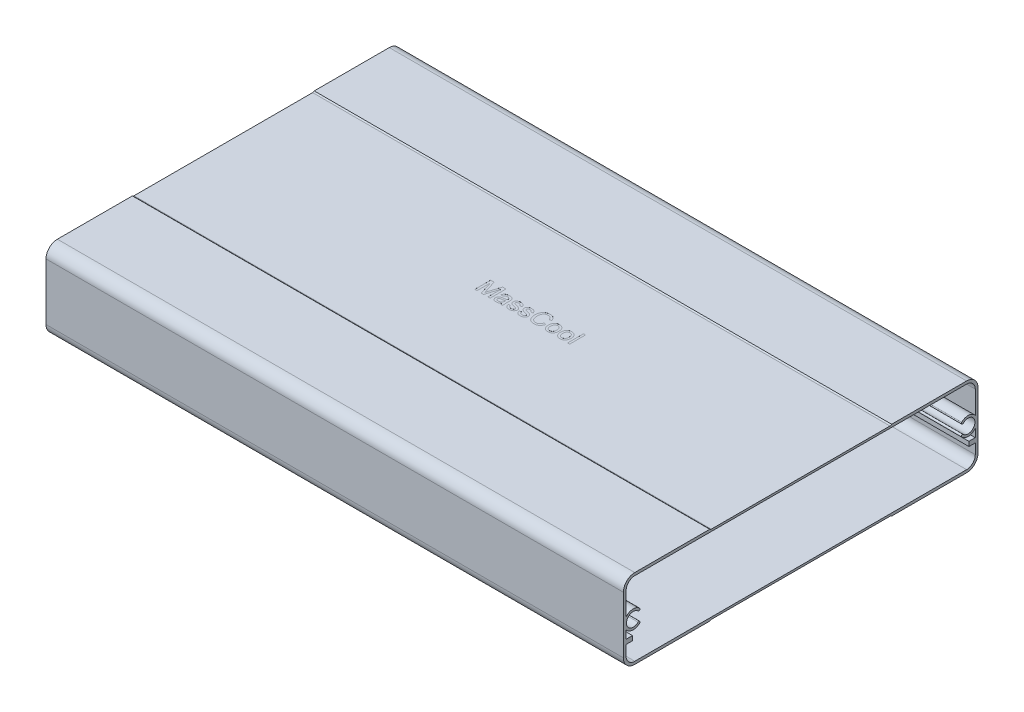
SolidWorks part; units mm, degrees
ref_plane "Alzado" through (0, 0, 0) normal (0, 0, 1) x (1, 0, 0)
ref_plane "Planta" through (0, 0, 0) normal (0, 1, 0) x (1, 0, 0)
ref_plane "Vista lateral" through (0, 0, 0) normal (1, 0, 0) x (0, 0, -1)
sketch "Croquis1" plane through (0, 0, 0) normal (1, 0, 0) x (0, 0, -1)
  line L1 (-36.5, 8.75) -> (36.5, 8.75)
  line L2 (-39, 6.25) -> (-39, -6.25)
  line L3 (-36.5, -8.75) -> (36.5, -8.75)
  line L4 (39, 6.25) -> (39, -6.25)
  line L5 (-39, 8.75) -> (39, -8.75) construction
  line L6 (-39, -8.75) -> (39, 8.75) construction
  arc A0 (-36.5, 8.75) -> (-39, 6.25) centre (-36.5, 6.25) ccw
  arc A1 (36.5, 8.75) -> (39, 6.25) centre (36.5, 6.25) cw
  arc A2 (36.5, -8.75) -> (39, -6.25) centre (36.5, -6.25) ccw
  arc A3 (-39, -6.25) -> (-36.5, -8.75) centre (-36.5, -6.25) ccw
  point P0 (0, 0)
  dimension "D3" = 2.5
  dimension "D1" = 78
  dimension "D2" = 17.5
extrude "Extruir-Lámina1" add sketch "Croquis1" along normal mid plane 127 thin thin type one direction reverse wall 0.6
sketch "Croquis2" plane through (63.5, 0, 0) normal (1, 0, 0) x (0, 0, -1)
  line L0 (36.5, 8.75) -> (-36.5, 8.75) construction
  line L1 (-20, 8.75) -> (20, 8.75)
  line L2 (-20, 8.75) -> (-20, 8.6)
  line L3 (-20, 8.6) -> (20, 8.6)
  line L4 (20, 8.75) -> (20, 8.6)
  line L5 (39, -6.25) -> (39, 6.25) construction
  line L6 (-39, 6.25) -> (-39, -6.25) construction
  dimension "D1" = 19
  dimension "D2" = 19
  dimension "D3" = 0.15
extrude "Extruir1" cut sketch "Croquis2" against normal through all
fillet "Redondeo1" radius 0.5 2 edges at (0, 8.6, 20) (0, 8.6, -20)
mirror "Simetría1" about plane through (0, 0, 0) normal (0, 1, 0) of "Redondeo1", "Extruir1"
sketch "Croquis3" plane through (63.5, 0, 0) normal (1, 0, 0) x (0, 0, -1)
  line L0 (-38.4, 6.25) -> (-38.4, -6.25) construction
  line L1 (-38.83, 6.25) -> (-38.83, -6.4355) construction
  line L2 (-39, 6.25) -> (-39, -6.25) construction
  line L3 (-36.83, 0) -> (-35.3812, -1.4488) construction
  line L4 (-36.83, 0) -> (-35.3812, 1.4488) construction
  line L7 (-36.5, -8.75) -> (-20, -8.75) construction
  line L8 (-38.4, -3) -> (-37, -3)
  line L9 (-38.4, -3) -> (-38.4, -4)
  line L10 (-38.4, -4) -> (-37, -4)
  line L11 (-37, -3) -> (-37, -4)
  arc A0 (-35.4158, 1.4142) -> (-35.4158, -1.4142) centre (-36.83, 0) ccw
  arc A1 (-35.7693, 1.0607) -> (-35.7693, -1.0607) centre (-36.83, 0) ccw
  arc A2 (-35.7693, 1.0607) -> (-35.4158, 1.4142) centre (-35.5926, 1.2374) ccw
  arc A3 (-35.4158, -1.4142) -> (-35.7693, -1.0607) centre (-35.5926, -1.2374) ccw
  point P5 (-38.4, 0)
  dimension "D1" = 4
  dimension "D2" = 3
  dimension "D7" = 1
  dimension "D3" = 0.17
  dimension "D4" = 90
  dimension "D5" = 2
  dimension "D6" = 1
extrude "Extruir2" add sketch "Croquis3" against normal through all
mirror "Simetría2" about plane through (0, 0, 0) normal (0, 0, 1) of "Extruir2"
sketch "Croquis4" plane through (0, 8.6, 0) normal (0, 1, 0) x (1, 0, 0)
  line L0 (-8.5, 0) -> (53.5, 0) construction
  line L1 (-63.5, -19.6429) -> (-63.5, 19.6429) construction
  line L2 (63.5, -19.6429) -> (63.5, 19.6429) construction
  text T0 "MassCool\r\n\r\n" font "MetroDF" height 3.5
  dimension "D1" = 55
  dimension "D2" = 10
extrude "Extruir4" cut sketch "Croquis4" against normal blind 0.005
